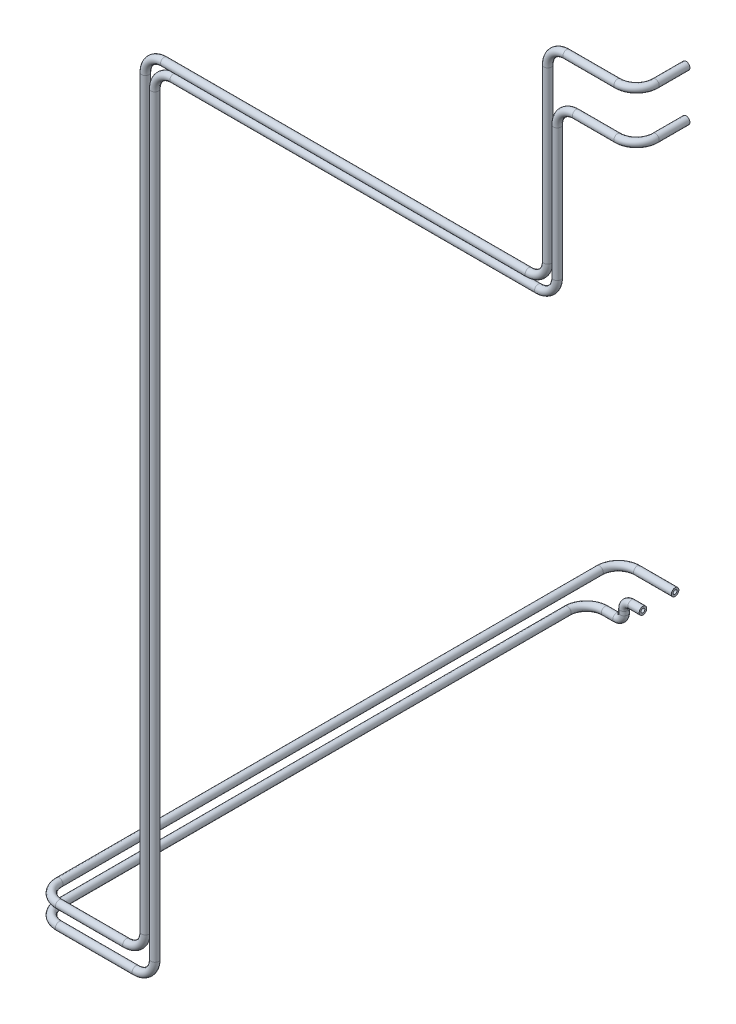
SolidWorks part; units mm, degrees
material "ABS"
ref_plane "Front Plane" through (0, 0, 0) normal (0, 0, 1) x (1, 0, 0)
ref_plane "Top Plane" through (0, 0, 0) normal (0, 1, 0) x (1, 0, 0)
ref_plane "Right Plane" through (0, 0, 0) normal (1, 0, 0) x (0, 0, -1)
sketch "Sketch1" plane through (0, 0, 0) normal (0, 0, 1) x (1, 0, 0)
  line L0 (0, 0) -> (-47, 0)
  line L1 (-47, 0) -> (-47, -110)
  line L2 (-47, -110) -> (-260, -110)
  line L3 (-260, -110) -> (-260, -524)
  line L4 (-260, -524) -> (-315.6, -524)
  point P7 (0, 0)
  dimension "D1" = 47
  dimension "D2" = 110
  dimension "D3" = 260
  dimension "D4" = 414
  dimension "D5" = 55.6
sketch "Sketch2" plane through (0, 0, 0) normal (1, 0, 0) x (0, 0, -1)
  line L0 (0, 0) -> (26.25, 0)
  line L1 (26.25, -25) -> (0, -25)
  point P3 (0, 0)
  point P4 (0, 0)
  dimension "D1" = 26.25
  dimension "D2" = 25
ref_plane "Plane1" through (0, 0, -26.25) normal (0, 0, 1) x (1, 0, 0)
ref_plane "Plane2" through (-315.6, 0, 0) normal (1, 0, 0) x (0, 0, -1)
sketch "Sketch5" plane through (-315.6, 0, 0) normal (1, 0, 0) x (0, 0, -1)
  line L0 (0, -524) -> (306, -524)
  line L1 (0, -110) -> (0, -524) construction
  point P4 (0, -536.568)
  point P5 (0, 0)
  dimension "D1" = 306
ref_plane "Plane3" through (0, 0, -306) normal (0, 0, 1) x (1, 0, 0)
sketch "Sketch6" plane through (0, 0, -306) normal (0, 0, 1) x (1, 0, 0)
  line L0 (-315.6, -524) -> (-285.6, -524)
  dimension "D1" = 30
sketch3d "3DSketch2"
  line L0 (0, 0, -26.25) -> (0, 0, -10)
  line L1 (-10, 0, 0) -> (-37, 0, 0)
  line L2 (-47, -10, 0) -> (-47, -100, 0)
  line L3 (-47, 0, 0) -> (-47, -110, 0) construction
  line L4 (-57, -110, 0) -> (-250, -110, 0)
  line L5 (-260, -120, 0) -> (-260, -514, 0)
  line L6 (-270, -524, 0) -> (-305.6, -524, 0)
  line L7 (-315.6, -524, -10) -> (-315.6, -524, -296)
  line L8 (-305.6, -524, -306) -> (-285.6, -524, -306)
  arc A0 (-315.6, -524, -296) -> (-305.6, -524, -306) centre (-305.6, -524, -296) ccw
  arc A1 (-305.6, -524, 0) -> (-315.6, -524, -10) centre (-305.6, -524, -10) ccw
  arc A2 (-260, -514, 0) -> (-270, -524, 0) centre (-270, -514, 0) ccw
  arc A3 (-250, -110, 0) -> (-260, -120, 0) centre (-250, -120, 0) ccw
  arc A4 (-47, -100, 0) -> (-57, -110, 0) centre (-57, -100, 0) ccw
  arc A5 (-37, 0, 0) -> (-47, -10, 0) centre (-37, -10, 0) ccw
  arc A6 (0, 0, -10) -> (-10, 0, 0) centre (-10, 0, -10) ccw
  point P21 (-315.6, -524, -306)
  point P22 (-305.6, -534, -296)
  point P25 (-315.6, -524, 0)
  point P26 (-305.6, -534, -10)
  point P29 (-260, -524, 0)
  point P30 (-270, -514, -10)
  point P33 (-260, -110, 0)
  point P34 (-250, -120, 10)
  point P37 (-47, -110, 0)
  point P38 (-57, -100, -10)
  point P41 (-47, 0, 0)
  point P42 (-37, -10, 10)
  point P45 (0, 0, 0)
  point P46 (-10, -10, -10)
  dimension "D1" = 10
sketch "Sketch7" plane through (0, 0, -26.25) normal (0, 0, 1) x (1, 0, 0)
  circle A0 centre (0, 0) radius 1
  circle A1 centre (0, 0) radius 2
  dimension "D1" = 2
  dimension "D2" = 4
sweep "Sweep2" add profiles "Sketch7" path "3DSketch2"
ref_axis "Axis1" through (0, 0, -26.25) along (0, 0, 1)
sketch "Sketch8" plane through (0, 0, 0) normal (0, 0, 1) x (1, 0, 0)
  line L0 (0, -25) -> (-42, -25)
  line L1 (-42, -25) -> (-42, -115)
  line L2 (-42, -115) -> (-255, -115)
  line L3 (-255, -115) -> (-255, -534)
  line L4 (-255, -534) -> (-315.6, -534)
  line L5 (-47, 0) -> (-47, -110) construction
  line L6 (-47, -110) -> (-260, -110) construction
  line L7 (-260, -110) -> (-260, -524) construction
  line L8 (-260, -524) -> (-315.6, -524) construction
  point P13 (-255, -529.9319)
  point P16 (0, 0)
  point P20 (0, 0)
  dimension "D1" = 5
  dimension "D2" = 5
  dimension "D3" = 5
  dimension "D4" = 10
sketch "Sketch9" plane through (-315.6, 0, 0) normal (1, 0, 0) x (0, 0, -1)
  line L0 (0, -534) -> (289, -534)
  point P3 (0, 0)
  point P4 (0, 0)
  dimension "D1" = 289
ref_plane "Plane4" through (0, 0, -289) normal (0, 0, 1) x (1, 0, 0)
sketch "Sketch10" plane through (0, 0, -289) normal (0, 0, 1) x (1, 0, 0)
  line L0 (-315.6, -534) -> (-295.6, -534)
  line L1 (-295.6, -534) -> (-295.6, -524)
  line L2 (-295.6, -524) -> (-285.6, -524)
  line L3 (-260, -524) -> (-315.6, -524) construction
  line L4 (-285.6, -526) -> (-285.6, -522) construction
  point P3 (-295.6, -524)
  point P8 (-285.6, -524)
  dimension "D1" = 20
sketch3d "3DSketch3"
  line L0 (0, -25, -26.25) -> (0, -25, -10)
  line L1 (0, -25, -26.25) -> (0, -25, 0) construction
  line L2 (-10, -25, 0) -> (-32, -25, 0)
  line L3 (-42, -35, 0) -> (-42, -105, 0)
  line L4 (-52, -115, 0) -> (-245, -115, 0)
  line L5 (-255, -125, 0) -> (-255, -524, 0)
  line L6 (-265, -534, 0) -> (-305.6, -534, 0)
  line L7 (-315.6, -534, -10) -> (-315.6, -534, -279)
  line L8 (-305.6, -534, -289) -> (-299.6, -534, -289)
  line L9 (-295.6, -530, -289) -> (-295.6, -528, -289)
  line L10 (-291.6, -524, -289) -> (-285.6, -524, -289)
  arc A0 (-315.6, -534, -279) -> (-305.6, -534, -289) centre (-305.6, -534, -279) ccw
  arc A1 (-305.6, -534, 0) -> (-315.6, -534, -10) centre (-305.6, -534, -10) ccw
  arc A2 (-255, -524, 0) -> (-265, -534, 0) centre (-265, -524, 0) ccw
  arc A3 (-245, -115, 0) -> (-255, -125, 0) centre (-245, -125, 0) ccw
  arc A4 (-42, -105, 0) -> (-52, -115, 0) centre (-52, -105, 0) ccw
  arc A5 (-32, -25, 0) -> (-42, -35, 0) centre (-32, -35, 0) ccw
  arc A6 (0, -25, -10) -> (-10, -25, 0) centre (-10, -25, -10) ccw
  arc A7 (-299.6, -534, -289) -> (-295.6, -530, -289) centre (-299.6, -530, -289) ccw
  arc A8 (-295.6, -528, -289) -> (-291.6, -524, -289) centre (-291.6, -528, -289) ccw
  point P23 (0, -25, -26.25)
  point P27 (-315.6, -534, -289)
  point P28 (-305.6, -544, -279)
  point P31 (-315.6, -534, 0)
  point P32 (-305.6, -544, -10)
  point P35 (-255, -534, 0)
  point P36 (-265, -524, -10)
  point P39 (-255, -115, 0)
  point P40 (-245, -125, 10)
  point P43 (-42, -115, 0)
  point P44 (-52, -105, -10)
  point P47 (-42, -25, 0)
  point P48 (-32, -35, 10)
  point P51 (0, -25, 0)
  point P52 (-10, -35, -10)
  point P53 (-295.6, -534, -289)
  point P55 (-299.6, -530, -285)
  point P58 (-295.6, -524, -289)
  point P60 (-291.6, -528, -293)
  point P61 (0, 0, 0)
  dimension "D1" = 10
  dimension "D2" = 4
sketch "Sketch11" plane through (0, 0, -26.25) normal (0, 0, 1) x (1, 0, 0)
  circle A0 centre (0, -25) radius 2
  circle A1 centre (0, -25) radius 1
  dimension "D1" = 2
  dimension "D2" = 4
sweep "Sweep3" add profiles "Sketch11" path "3DSketch3"
